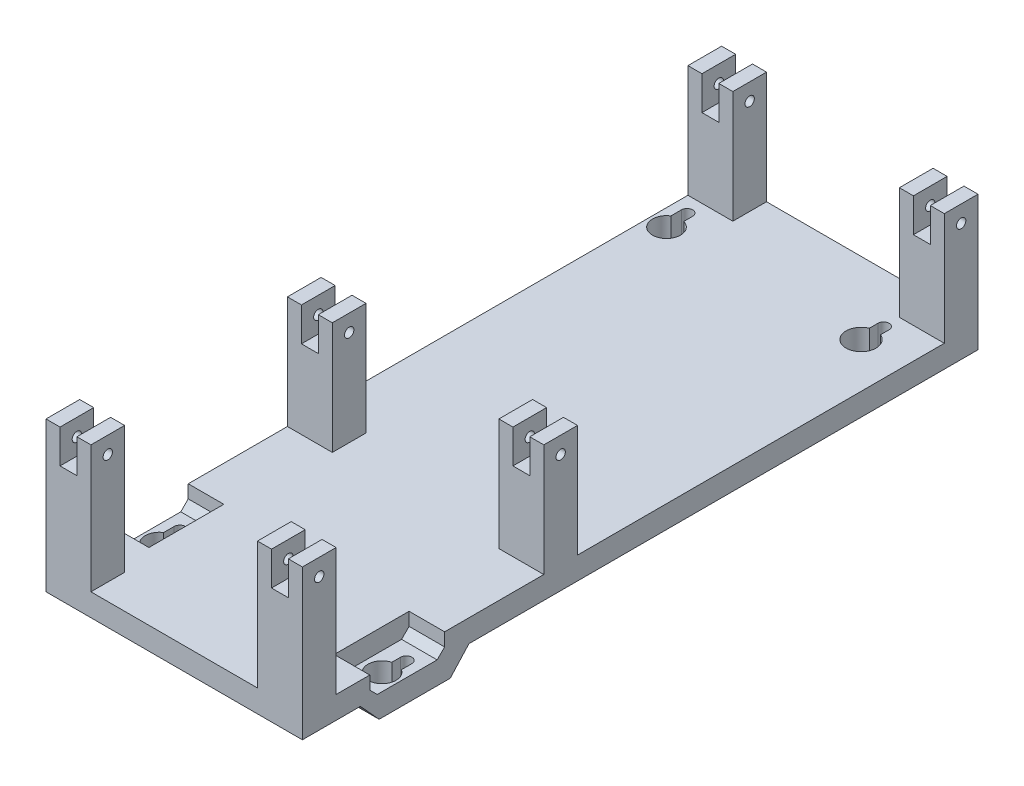
SolidWorks part; units mm, degrees
ref_plane "Front Plane" through (0, 0, 0) normal (0, 0, 1) x (1, 0, 0)
ref_plane "Top Plane" through (0, 0, 0) normal (0, 1, 0) x (1, 0, 0)
ref_plane "Right Plane" through (0, 0, 0) normal (1, 0, 0) x (0, 0, -1)
sketch "Sketch1" plane through (0, 0, 0) normal (0, 1, 0) x (1, 0, 0)
  line L1 (0, 0) -> (-68.5, 0)
  line L2 (0, 0) -> (0, 64.5)
  line L3 (0, 64.5) -> (-68.5, 64.5)
  line L4 (-68.5, 0) -> (-68.5, 64.5)
  dimension "D1" = 64.5
  dimension "D2" = 68.5
extrude "Boss-Extrude3" add sketch "Sketch1" along normal blind 21
sketch "Sketch3" plane through (0, 21, 0) normal (0, 1, 0) x (1, 0, 0)
  line L0 (0, 64.5) -> (-68.5, 64.5) construction
  line L1 (-65, 64.5) -> (-3.5, 64.5)
  line L2 (-65, 64.5) -> (-65, 3.5)
  line L3 (-65, 3.5) -> (-3.5, 3.5)
  line L4 (-3.5, 64.5) -> (-3.5, 3.5)
  line L5 (-68.5, 64.5) -> (-68.5, 0) construction
  line L6 (-68.5, 0) -> (0, 0) construction
  line L7 (0, 0) -> (0, 64.5) construction
  dimension "D1" = 3.5
  dimension "D2" = 3.5
  dimension "D3" = 3.5
extrude "Cut-Extrude1" cut sketch "Sketch3" against normal blind 15
sketch "Sketch5" plane through (0, 0, -64.5) normal (0, 0, -1) x (-1, 0, 0)
  line L0 (68.5, 21) -> (68.5, 0) construction
  line L1 (0, 0) -> (68.5, 0)
  line L2 (0, 0) -> (0, 6)
  line L3 (0, 6) -> (68.5, 6)
  line L4 (68.5, 0) -> (68.5, 6)
  dimension "D1" = 6
extrude "Boss-Extrude4" add sketch "Sketch5" along normal blind 105
sketch "Sketch9" plane through (0, 21, 0) normal (0, 1, 0) x (1, 0, 0)
  line L0 (-3.5, 3.5) -> (-3.5, 64.5) construction
  line L1 (-3.5, 38) -> (0, 38)
  line L2 (-3.5, 38) -> (-3.5, 18)
  line L3 (-3.5, 18) -> (0, 18)
  line L4 (0, 38) -> (0, 18)
  line L5 (0, 0) -> (0, 64.5) construction
  line L6 (-3.5, 64.5) -> (0, 64.5) construction
  dimension "D1" = 20
  dimension "D2" = 26.5
sketch "Sketch10" plane through (0, 0, 0) normal (0, -1, 0) x (1, 0, 0)
  line L0 (0, 0) -> (0, -169.5) construction
  line L1 (0, -15.5) -> (-10, -15.5)
  line L2 (0, -15.5) -> (0, -44.5)
  line L3 (0, -44.5) -> (-10, -44.5)
  line L4 (-10, -15.5) -> (-10, -44.5)
  line L5 (-68.5, 0) -> (0, 0) construction
  dimension "D1" = 15.5
  dimension "D2" = 10
  dimension "D3" = 29
extrude "Boss-Extrude5" add sketch "Sketch10" along normal blind 5.5
extrude "Cut-Extrude2" cut sketch "Sketch9" against normal blind 20.5
sketch "Sketch11" plane through (0, 6, 0) normal (0, 1, 0) x (1, 0, 0)
  line L1 (-3.5, 38) -> (-9.5, 38)
  line L2 (-3.5, 38) -> (-3.5, 18)
  line L3 (-3.5, 18) -> (-9.5, 18)
  line L4 (-9.5, 38) -> (-9.5, 18)
  dimension "D1" = 20
  dimension "4" = 6
extrude "Cut-Extrude3" cut sketch "Sketch11" against normal blind 5.5
chamfer "Chamfer2" distance 5.5 distance2 5 2 edges at (-5, -5.5, -44.5) (-5, -5.5, -15.5) first distance on face at (-6.25, -3.4375, -44.5) first distance on face at (-3.75, -3.4375, -15.5)
chamfer "Chamfer3" distance 2 angle 45 2 edges at (-4.75, 0.5, -38) (-4.75, 0.5, -18)
sketch "Sketch12" plane through (0, 21, 0) normal (0, 1, 0) x (1, 0, 0)
  line L1 (-68.5, 0) -> (-34.25, 0)
  line L2 (-68.5, 0) -> (-68.5, 169.5)
  line L3 (-68.5, 169.5) -> (-34.25, 169.5)
  line L4 (-34.25, 0) -> (-34.25, 169.5)
  dimension "D1" = 169.5
  dimension "D2" = 34.25
extrude "Cut-Extrude4" cut sketch "Sketch12" against normal blind 50
sketch "Sketch15" plane through (0, 0.5, 0) normal (0, 1, 0) x (1, 0, 0)
  line L0 (0, 20) -> (0, 36) construction
  line L1 (0, 36) -> (-9.5, 36) construction
  circle A0 centre (-4, 31.7571) radius 1.5
  dimension "D1" = 4
  dimension "D2" = 3
  dimension "D3" = 4.2429
extrude "Cut-Extrude5" cut sketch "Sketch15" against normal blind 50
sketch "Sketch19" plane through (0, 0, -169.5) normal (0, 0, -1) x (-1, 0, 0)
  line L1 (0, 6) -> (34.25, 6)
  line L2 (0, 6) -> (0, 0)
  line L3 (0, 0) -> (34.25, 0)
  line L4 (34.25, 6) -> (34.25, 0)
extrude "Boss-Extrude6" add sketch "Sketch19" along normal blind 11
sketch "Sketch26" plane through (0, 6, 0) normal (0, 1, 0) x (1, 0, 0)
  line L1 (0, 64.5) -> (-12, 64.5)
  line L2 (0, 64.5) -> (0, 73.5)
  line L3 (0, 73.5) -> (-12, 73.5)
  line L4 (-12, 64.5) -> (-12, 73.5)
  line L5 (-34.25, 0) -> (0, 0) construction
  line L6 (0, 180.5) -> (0, 64.5) construction
  line L8 (0, 0) -> (-12, 0)
  line L9 (0, 0) -> (0, 9)
  line L10 (0, 9) -> (-12, 9)
  line L11 (-12, 0) -> (-12, 9)
  line L12 (0, 180.5) -> (-12, 180.5)
  line L13 (0, 180.5) -> (0, 171.5)
  line L14 (0, 171.5) -> (-12, 171.5)
  line L15 (-12, 180.5) -> (-12, 171.5)
  dimension "D1" = 9
  dimension "D2" = 12
  dimension "D3" = 64.5
extrude "Boss-Extrude7" add sketch "Sketch26" along normal blind 30
sketch "Sketch20" plane through (0, 0.5, 0) normal (0, 1, 0) x (1, 0, 0)
  line L0 (0, 20) -> (0, 36) construction
  circle A0 centre (-4.5, 25.778) radius 3.75
  circle A2 centre (-4, 31.7571) radius 1.5 construction
  dimension "D1" = 4.5
  dimension "D2" = 7.5
  dimension "D3" = 6
extrude "Cut-Extrude9" cut sketch "Sketch20" against normal through all
sketch "Sketch21" plane through (0, 0.5, 0) normal (0, 1, 0) x (1, 0, 0)
  line L1 (-5.5, 31.7571) -> (-2.5, 31.7571)
  line L2 (-5.5, 31.7571) -> (-5.5, 28.9502)
  line L3 (-5.5, 28.9502) -> (-2.5, 28.9502)
  line L4 (-2.5, 31.7571) -> (-2.5, 28.9502)
  circle A4 centre (-4, 31.7571) radius 1.5 construction
  circle A5 centre (-4.5, 25.778) radius 3.75 construction
extrude "Cut-Extrude10" cut sketch "Sketch21" against normal through all
ref_plane "Plane1" through (-34.25, 0, 0) normal (1, 0, 0) x (0, 0, -1)
mirror "Mirror5" about plane through (-34.25, 0, 0) normal (1, 0, 0) of bodies 117 125
sketch "Sketch18" plane through (0, 6, 0) normal (0, 1, 0) x (1, 0, 0)
  line L0 (0, 171.5) -> (0, 73.5) construction
  circle A0 centre (-12, 167.2571) radius 1.5
  arc A2 (-2.5, 31.7571) -> (-5.5, 31.7571) centre (-4, 31.7571) ccw construction
  dimension "D1" = 135.5
  dimension "D2" = 3
  dimension "D3" = 12
extrude "Cut-Extrude8" cut sketch "Sketch18" against normal blind 135
sketch "Sketch24" plane through (0, 6, 0) normal (0, 1, 0) x (1, 0, 0)
  circle A0 centre (-12, 161.2571) radius 4
  circle A2 centre (-12, 167.2571) radius 1.5
  dimension "D2" = 8
  dimension "D1" = 6
extrude "Cut-Extrude13" cut sketch "Sketch24" against normal through all contours A0
sketch "Sketch25" plane through (0, 6, 0) normal (0, 1, 0) x (1, 0, 0)
  line L1 (-13.5, 167.2571) -> (-10.5, 167.2571)
  line L2 (-13.5, 167.2571) -> (-13.5, 164.0385)
  line L3 (-13.5, 164.0385) -> (-10.5, 164.0385)
  line L4 (-10.5, 167.2571) -> (-10.5, 164.0385)
  circle A2 centre (-12, 167.2571) radius 1.5 construction
extrude "Cut-Extrude14" cut sketch "Sketch25" against normal through all
sketch "Sketch33" plane through (0, 6, 0) normal (0, 1, 0) x (1, 0, 0)
  circle A0 centre (-64.5, 167.2571) radius 1.5
  arc A1 (-63, 31.7571) -> (-66, 31.7571) centre (-64.5, 31.7571) ccw construction
  circle A2 centre (-64.5, 31.7571) radius 1.5
  circle A3 centre (-12, 167.2571) radius 1.5
extrude "Cut-Extrude17" cut sketch "Sketch33" against normal blind 9.74
sketch "Sketch34" plane through (0, 6, 0) normal (0, 1, 0) x (1, 0, 0)
  line L0 (-68.5, 171.5) -> (-68.5, 73.5) construction
  circle A0 centre (-64, 161.278) radius 3.75
  circle A1 centre (-64.5, 167.2571) radius 1.5 construction
  dimension "D1" = 6
  dimension "7.5" = 7.5
  dimension "D2" = 4.5
extrude "Cut-Extrude18" cut sketch "Sketch34" against normal through all
sketch "Sketch39" plane through (0, 6, 0) normal (0, 1, 0) x (1, 0, 0)
  line L2 (-66, 167.2571) -> (-63, 167.2571)
  line L3 (-66, 167.2571) -> (-66, 162.786)
  line L4 (-66, 162.786) -> (-63, 162.786)
  line L5 (-63, 167.2571) -> (-63, 162.786)
  circle A0 centre (-64.5, 167.2571) radius 1.5 construction
extrude "Cut-Extrude22" cut sketch "Sketch39" against normal through all
sketch "Sketch40" plane through (0, 21, 0) normal (0, 1, 0) x (1, 0, 0)
  line L0 (-68.5, 64.5) -> (-68.5, 9)
  line L1 (-68.5, 9) -> (-68.5, 18) construction
  line L2 (-68.5, 9) -> (-56.5, 9)
  line L3 (-68.5, 64.5) -> (0, 64.5)
  line L4 (-56.5, 9) -> (-56.5, 0)
  line L5 (-56.5, 0) -> (-12, 0) construction
  line L6 (-56.5, 0) -> (-12, 0)
  line L7 (-12, 0) -> (-12, 9)
  line L8 (-12, 9) -> (0, 9)
  line L9 (0, 9) -> (0, 18) construction
  line L10 (0, 9) -> (0, 64.5)
  dimension "D1" = 9
  dimension "D2" = 9
  dimension "D3" = 12
  dimension "D4" = 12
extrude "Cut-Extrude23" cut sketch "Sketch40" against normal blind 15
sketch "Sketch41" plane through (0, 36, 0) normal (0, 1, 0) x (1, 0, 0)
  line L0 (-56.5, 64.5) -> (-68.5, 64.5) construction
  line L1 (-64.75, 64.5) -> (-60.25, 64.5)
  line L2 (-64.75, 64.5) -> (-64.75, 73.5)
  line L3 (-64.75, 73.5) -> (-60.25, 73.5)
  line L4 (-60.25, 64.5) -> (-60.25, 73.5)
  line L5 (-68.5, 73.5) -> (-56.5, 73.5) construction
  line L6 (-56.5, 171.5) -> (-68.5, 171.5) construction
  line L7 (-64.75, 171.5) -> (-60.25, 171.5)
  line L8 (-64.75, 171.5) -> (-64.75, 180.5)
  line L9 (-64.75, 180.5) -> (-60.25, 180.5)
  line L10 (-60.25, 171.5) -> (-60.25, 180.5)
  line L11 (-68.5, 180.5) -> (-56.5, 180.5) construction
  line L12 (-12, 64.5) -> (0, 64.5) construction
  line L13 (-8.25, 64.5) -> (-3.75, 64.5)
  line L14 (-8.25, 64.5) -> (-8.25, 73.5)
  line L15 (-8.25, 73.5) -> (-3.75, 73.5)
  line L16 (-3.75, 64.5) -> (-3.75, 73.5)
  line L17 (0, 73.5) -> (-12, 73.5) construction
  line L18 (-12, 171.5) -> (0, 171.5) construction
  line L19 (-8.25, 171.5) -> (-3.75, 171.5)
  line L20 (-8.25, 171.5) -> (-8.25, 180.5)
  line L21 (-8.25, 180.5) -> (-3.75, 180.5)
  line L22 (-3.75, 171.5) -> (-3.75, 180.5)
  line L23 (0, 180.5) -> (-12, 180.5) construction
  line L24 (0, 64.5) -> (0, 73.5) construction
  line L26 (-56.5, 73.5) -> (-56.5, 64.5) construction
  line L27 (-68.5, 64.5) -> (-68.5, 73.5) construction
  line L28 (-56.5, 180.5) -> (-56.5, 171.5) construction
  line L29 (-68.5, 171.5) -> (-68.5, 180.5) construction
  line L30 (-12, 180.5) -> (-12, 171.5) construction
  line L31 (0, 171.5) -> (0, 180.5) construction
  dimension "D1" = 3.75
  dimension "D2" = 4.5
  dimension "D3" = 3.75
extrude "Cut-Extrude24" cut sketch "Sketch41" against normal blind 9
sketch "Sketch42" plane through (0, 0, 0) normal (1, 0, 0) x (0, 0, -1)
  line L0 (73.5, 36) -> (73.5, 6) construction
  line L1 (64.5, 36) -> (73.5, 36) construction
  line L2 (180.5, 36) -> (180.5, 0) construction
  circle A0 centre (69, 31.5) radius 1.25
  circle A1 centre (176, 31.5) radius 1.25
  dimension "D1" = 2.5
  dimension "D2" = 4.5
  dimension "D3" = 4.5
  dimension "D4" = 4.5
extrude "Cut-Extrude25" cut sketch "Sketch42" against normal through all
sketch "Sketch43" plane through (0, 36, 0) normal (0, 1, 0) x (1, 0, 0)
  line L1 (-56.5, 0) -> (-68.5, 0)
  line L2 (-56.5, 0) -> (-56.5, 9)
  line L3 (-56.5, 9) -> (-68.5, 9)
  line L4 (-68.5, 0) -> (-68.5, 9)
  line L5 (-12, 9) -> (0, 9)
  line L6 (-12, 9) -> (-12, 0)
  line L7 (-12, 0) -> (0, 0)
  line L8 (0, 9) -> (0, 0)
extrude "Boss-Extrude8" add sketch "Sketch43" along normal blind 4
sketch "Sketch44" plane through (0, 40, 0) normal (0, 1, 0) x (1, 0, 0)
  line L0 (-68.5, 0) -> (-56.5, 0) construction
  line L1 (-64.75, 0) -> (-60.25, 0)
  line L2 (-64.75, 0) -> (-64.75, 9)
  line L3 (-64.75, 9) -> (-60.25, 9)
  line L4 (-60.25, 0) -> (-60.25, 9)
  line L5 (-56.5, 9) -> (-68.5, 9) construction
  line L6 (-12, 0) -> (0, 0) construction
  line L7 (-8.25, 0) -> (-3.75, 0)
  line L8 (-8.25, 0) -> (-8.25, 9)
  line L9 (-8.25, 9) -> (-3.75, 9)
  line L10 (-3.75, 0) -> (-3.75, 9)
  line L11 (0, 9) -> (-12, 9) construction
  line L12 (-56.5, 0) -> (-56.5, 9) construction
  line L13 (-12, 9) -> (-12, 0) construction
  dimension "D1" = 4.5
  dimension "D2" = 3.75
  dimension "D3" = 4.5
  dimension "D4" = 3.75
extrude "Cut-Extrude26" cut sketch "Sketch44" against normal blind 9
sketch "Sketch45" plane through (0, 0, 0) normal (1, 0, 0) x (0, 0, -1)
  line L0 (9, 40) -> (9, 6) construction
  line L1 (0, 40) -> (9, 40) construction
  circle A0 centre (4.5, 35.5) radius 1.25
  dimension "D1" = 2.5
  dimension "D2" = 4.5
  dimension "D3" = 4.5
extrude "Cut-Extrude27" cut sketch "Sketch45" against normal through all
equation "\"5.5.00mm\"=15"
